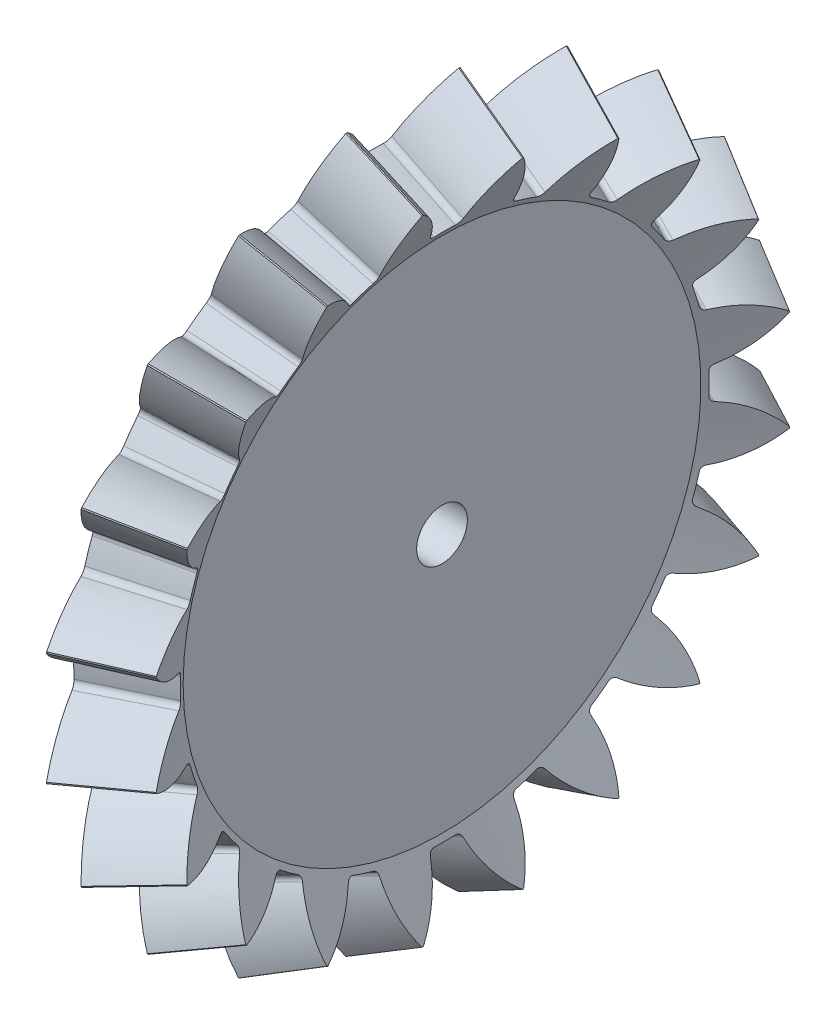
SolidWorks part; units mm, degrees
revolve "Base-Revolve" add sketch "BasProSke" angle 360 about L0 other way angle 9
sketch "BasProSke" plane through (0, 0, 0) normal (0, 1, 0) x (1, 0, 0)
  line L0 (-10, 0) -> (60, 0) construction
  line L1 (0, 0) -> (0, 45.9553)
  line L2 (0, 0) -> (11.6301, 0)
  line L3 (11.6301, 0) -> (11.6301, 40.8173)
  line L4 (104.0224, 0) -> (-25.9395, 64.9809) construction
  line L5 (0, 45.9553) -> (5.478, 56.9113)
  line L6 (104.0224, 0) -> (-24.5296, 74.2412) construction
  line L7 (104.0224, 0) -> (0, 45.9553) construction
  line L8 (5.478, 56.9113) -> (16.4956, 50.5484)
  line L9 (16.4956, 50.5484) -> (11.6301, 40.8173)
  line L10 (2.4224, 50.8) -> (-9.562, 50.8) construction
  dimension "D1" = 91.9106
  dimension "D2" = 104.0224
  dimension "D3" = 113.5923
  dimension "D4" = 3.442
ref_plane "Plane1" through (0, 0, 0) normal (0, 0, 1) x (1, 0, 0)
ref_plane "Plane2" through (0, 0, 0) normal (0, 1, 0) x (1, 0, 0)
ref_plane "Plane3" through (0, 0, 0) normal (1, 0, 0) x (0, 0, -1)
sketch "HoldingSke" plane through (0, 0, 0) normal (0, 1, 0) x (1, 0, 0)
  line L0 (0, 0) -> (119.341, -43.4366)
  line L1 (-15, 0) -> (100, 0) construction
  line L2 (0, 0) -> (-3.4367, 41.6724)
  line L3 (0, 0) -> (-11.863, 4.5341)
  line L4 (0, 0) -> (8.1152, 2.9537)
  line L5 (0, 0) -> (-66.6361, -24.8533)
  line L6 (0, 0) -> (-10.5278, -7.1032)
  line L7 (-3.4367, 41.6724) -> (46.0871, 133.1495)
  line L8 (-76.2, 54.61) -> (-54.9402, 54.61)
  line L9 (-71.009, 38.7566) -> (-53.1078, 45.2721)
  line L10 (-76.2, 71.12) -> (104.1128, 71.12)
  line L11 (0, 0) -> (-12.7, 0)
  line L12 (-76.2, 101.6) -> (-76.0095, 101.6)
  line L13 (24.9733, 27.94) -> (52.9484, 28.5968)
  line L14 (24.9733, 27.94) -> (25.0241, 27.9398)
  line L15 (24.9733, 27.94) -> (100.4104, 29.05)
  line L16 (-3.4367, 41.6724) -> (95.4653, -41.3162)
  circle A0 centre (0, 0) radius 9.525
  circle A1 centre (0, 0) radius 15.24
  circle A2 centre (0, 0) radius 15.24
  circle A3 centre (0, 0) radius 9.525
  dimension "Num_teeth" = 20
  dimension "Pitch_radius" = 180.3128
  dimension "Width" = 12.7
ref_plane "ToothPln" through (2.739, 51.4333, 0) normal (-0.8944, 0.4472, 0) x (0, 0, -1)
ref_plane "ToothPln2" through (83.2179, -41.6089, 0) normal (-0.8944, 0.4472, 0) x (0, 0, 1)
sketch "TooCutSke" plane through (2.739, 51.4333, 0) normal (-0.8944, 0.4472, 0) x (0, 0, -1)
  line L2 (0, 51.508) -> (270.6104, -1657.059) construction
  line L3 (0, 51.508) -> (146.0561, -1760.7306) construction
  line L4 (0, -15.621) -> (0, 105.791) construction
  line L6 (-24.765, -6.1246) -> (21.082, -6.1246) construction
  line L7 (7.9469, 1.3335) -> (4.069, 1.0209) construction
  arc A0 (-9.8853, -6.4401) -> (9.8853, -6.4401) centre (0, 51.508) ccw
  arc A1 (-1.8822, 5.0794) -> (1.8822, 5.0794) centre (0, 51.508) ccw
  circle A2 centre (0, 51.508) radius 50.8 construction
  circle A3 centre (0, 51.508) radius 47.7364 construction
  arc A4 (2.8964, 4.3275) -> (1.8822, 5.0794) centre (1.9229, 4.0744) ccw
  arc A5 (2.8964, 4.3275) -> (9.8853, -6.4401) centre (22.5626, 9.4403) ccw
  arc A6 (-9.8853, -6.4401) -> (-2.8964, 4.3275) centre (-22.5626, 9.4403) ccw
  arc A7 (-1.8822, 5.0794) -> (-2.8964, 4.3275) centre (-1.9229, 4.0744) ccw
  ellipse E0 centre (0, 44.7784) end of major axis (56.9113, 44.7784) minor radius 50.903 construction
sketch "TooCutSke2" plane through (83.2179, -41.6089, 0) normal (-0.8944, 0.4472, 0) x (0, 0, 1)
  line L0 (0, 0) -> (0, 68.072) construction
  line L2 (21.082, 41.1037) -> (-20.32, 41.1037) construction
  circle A0 centre (0, 46.5202) radius 0.0127
  ellipse E1 centre (0, 0) end of major axis (-45.9553, 0) minor radius 41.1037 construction
loft "ToothCut" cut profiles "TooCutSke2", "TooCutSke"
pattern_circular "TeethCuts" count 20 every 18 about axis through (-10, 0, 0) along (1, 0, 0) of "ToothCut"
sketch "HubSke" plane through (0, 0, 0) normal (-1, 0, 0) x (0, 0, 1)
  circle A0 centre (0, 0) radius 15.24
  dimension "Diameter" = 30.48
extrude "Hub" add sketch "HubSke" along normal blind 0.0001
sketch "BorSke" plane through (0, 0, 0) normal (1, 0, 0) x (0, 0, -1)
  circle A0 centre (0, 0) radius 4
  dimension "Diameter" = 8
extrude "Bore" cut sketch "BorSke" along normal mid plane 208.0448
sketch "KeySke" plane through (0, 0, 0) normal (1, 0, 0) x (0, 0, -1)
  line L0 (-2.3813, 0) -> (-2.3813, 11.7348)
  line L1 (-2.3813, 11.7348) -> (2.3813, 11.7348)
  line L2 (2.3813, 11.7348) -> (2.3813, 0)
  line L3 (0, 0) -> (0, 34) construction
  line L4 (-2.3813, 0) -> (2.3813, 0)
  dimension "Offset" = 11.7348
extrude "Keyway" [suppressed] cut sketch "KeySke" along normal mid plane 208.0448
pattern_circular "Keyway2" [suppressed] count 2 every 90 about axis through (-10, 0, 0) along (1, 0, 0)
equation "' \"Pitch@HoldingSke\" = 4"
equation "' \"Num_teeth@HoldingSke\" = 12"
equation "' \"Mating_teeth@HoldingSke\" = 20"
equation "' \"Ap@HoldingSke\" =  20"
equation "' \"Ap@HoldingSke\" = 20"
equation "' \"Width@HoldingSke\" = 0.5"
equation "' \"Hub_dia@HoldingSke\"= 2"
equation "' \"Hub_dia@HoldingSke\" = 2"
equation "' \"Mounting_dist@HoldingSke\" = 3"
equation "' \"Bore@HoldingSke\" = 0.75"
equation "' \"T_dim@HoldingSke\" = 0.85"
equation "' \"Width@KeySke\" = 0.25"
equation "' \"Show_teeth@HoldingSke\" = 100"
equation "' \"Backlash@HoldingSke\" = 0.009"
equation "' \"Addendum_fac@HoldingSke\" = 1.0"
equation "' \"Dedendum_fac@HoldingSke\" = 1.188"
equation "' \"Dedendum_add@HoldingSke\" = 0.002"
equation "' \"Clearance_fac@HoldingSke\" = 0.188"
equation "' \"Addendum_fac@HoldingSke\" = 0.54 + 0.46 / (\"Num_teeth@HoldingSke\" /  \"Mating_teeth@HoldingSke\" ) ^ 2"
equation " \"Addendum_fac@HoldingSke\" = 2 - (0.54 + 0.46 / (\"Mating_teeth@HoldingSke\" /  \"Num_teeth@HoldingSke\" ) ^ 2)"
equation "\"Dedendum_fac@HoldingSke\" = 2.188 - \"Addendum_fac@HoldingSke\""
equation "\"Pitch_rad@BasProSke\" = \"Num_teeth@HoldingSke\" / \"Pitch@HoldingSke\" / 2"
equation "\"Pitch_ang@BasProSke\" = atn(\"Num_teeth@HoldingSke\" / \"Mating_teeth@HoldingSke\") * (180 / 3.14159265)"
equation "\"Addendum@BasProSke\" = \"Addendum_fac@HoldingSke\" / \"Pitch@HoldingSke\""
equation "\"Dedendum_plus@BasProSke\" = (\"Dedendum_fac@HoldingSke\" / \"Pitch@HoldingSke\" + \"Dedendum_add@HoldingSke\") * 1.25"
equation "\"Face_wid@BasProSke\" = \"Width@HoldingSke\""
equation "\"Radius@TooCutSke\" = ((\"Num_teeth@HoldingSke\" + 2 * \"Addendum_fac@HoldingSke\") / \"Pitch@HoldingSke\" ) / 2"
equation "\"Overcut_dia@TooCutSke\" =  1.02 * (\"Num_teeth@HoldingSke\" + 2 * \"Addendum_fac@HoldingSke\") / \"Pitch@HoldingSke\""
equation "\"Pitch_dia@TooCutSke\" = \"Num_teeth@HoldingSke\" / \"Pitch@HoldingSke\""
equation "\"Base_dia@TooCutSke\" = \"Num_teeth@HoldingSke\" / \"Pitch@HoldingSke\" * cos((\"Ap@HoldingSke\"  * 3.14159265 / 180))"
equation "'  \"Root_dia@TooCutSke\" =  (\"Num_teeth@HoldingSke\" + 2) / \"Pitch@HoldingSke\" - 2 * (\"Addendum_fac@HoldingSke\" + \"Dedendum_fac@HoldingSke\") / \"Pitch@HoldingSke\" - \"Dedendum_add@HoldingSke\" * 2"
equation "'  \"Root_dia@TooCutSke\" = (\"Num_teeth@HoldingSke\" + 2) / \"Pitch@HoldingSke\" - 2 * (\"Addendum_fac@HoldingSke\" + \"Dedendum_fac@HoldingSke\") / \"Pitch@HoldingSke\" - \"Dedendum_add@HoldingSke\" * 2"
equation "\"Root_dia@TooCutSke\" =  \"Num_teeth@HoldingSke\" / \"Pitch@HoldingSke\" -  2 * \"Dedendum_fac@HoldingSke\" / \"Pitch@HoldingSke\" - \"Dedendum_add@HoldingSke\" * 2"
equation "\"Half_ang@TooCutSke\" = 180 / \"Num_teeth@HoldingSke\""
equation "\"Half_CT@TooCutSke\" = \"Num_teeth@HoldingSke\" / \"Pitch@HoldingSke\" * sin((3.14159265 / 2 / \"Num_teeth@HoldingSke\")) / 2 - 2 * \"Backlash@HoldingSke\" / 4"
equation "\"Flank_rad@TooCutSke\" = \"Num_teeth@HoldingSke\" / \"Pitch@HoldingSke\" / 5"
equation "\"Root_fillet@TooCutSke\" = \"Clearance_fac@HoldingSke\" / \"Pitch@HoldingSke\" + \"Dedendum_add@HoldingSke\""
equation "\"Offset@ToothPln2\"  = \"Num_teeth@HoldingSke\" / \"Pitch@HoldingSke\" / 2 / sin(atn(\"Num_teeth@HoldingSke\" / \"Mating_teeth@HoldingSke\"))"
equation "\"Dedendum_plus@TooCutSke2\" = \"Dedendum_plus@BasProSke\""
equation "\"MHD@HoldingSke\" = \"Num_teeth@HoldingSke\" / \"Pitch@HoldingSke\" - 2 * \"Dedendum_plus@BasProSke\" * cos(atn(\"Num_teeth@HoldingSke\" / \"Mating_teeth@HoldingSke\"))"
equation "\"MBD@HoldingSke\" = \"Num_teeth@HoldingSke\" / \"Pitch@HoldingSke\" - 2 * \"Dedendum_plus@BasProSke\" * cos(atn(\"Num_teeth@HoldingSke\" / \"Mating_teeth@HoldingSke\")) - 0.002"
equation "\"MnMD@HoldingSke\" =  \"Num_teeth@HoldingSke\" / \"Pitch@HoldingSke\" / 2 / (\"Num_teeth@HoldingSke\" / \"Mating_teeth@HoldingSke\") + \"Dedendum_plus@BasProSke\" * sin(atn(\"Num_teeth@HoldingSke\" / \"Mating_teeth@HoldingSke\"))"
equation "\"OAL@HoldingSke\" = \"MnMD@HoldingSke\""
equation "\"MHD@HoldingSke\" = ((sgn( \"MHD@HoldingSke\" - \"Hub_dia@HoldingSke\" )-1)*( \"MHD@HoldingSke\" - \"Hub_dia@HoldingSke\" ))/-2+ \"Hub_dia@HoldingSke\""
equation "\"MBD@HoldingSke\" = ((sgn( \"MBD@HoldingSke\" - \"Bore@HoldingSke\" )-1)*( \"MBD@HoldingSke\" - \"Bore@HoldingSke\" ))/-2+ \"Bore@HoldingSke\""
equation "\"Face_wid@BasProSke\" = ((sgn( \"Face_wid@BasProSke\" - \"Offset@ToothPln2\" * 0.9)-1)*( \"Face_wid@BasProSke\" - \"Offset@ToothPln2\" * 0.9))/-2+ \"Offset@ToothPln2\" * 0.9"
equation "\"OAL@HoldingSke\" = ((sgn( \"OAL@HoldingSke\" - \"Mounting_dist@HoldingSke\" )+1)*( \"OAL@HoldingSke\" - \"Mounting_dist@HoldingSke\" ))/2 + \"Mounting_dist@HoldingSke\" + 0.000002"
equation "\"Num_teeth@TeethCuts\" = int( \"Show_teeth@HoldingSke\" ) + 1"
equation "\"Num_teeth@TeethCuts\" = ((sgn( \"Num_teeth@TeethCuts\" - \"Num_teeth@HoldingSke\" )-1)*( \"Num_teeth@TeethCuts\" - \"Num_teeth@HoldingSke\" ))/-2+ \"Num_teeth@HoldingSke\""
equation "\"Num_teeth@TeethCuts\" = ((sgn( \"Num_teeth@TeethCuts\" - 2.0)+1)*( \"Num_teeth@TeethCuts\" - 2.0))/2 +2.0"
equation "\"Angle@TeethCuts\" = 360.0 / \"Num_teeth@HoldingSke\""
equation "\"Diameter@HubSke\" = \"MHD@HoldingSke\""
equation "\"Length@Hub\" = \"OAL@HoldingSke\" - \"MnMD@HoldingSke\" + 0.000002"
equation "\"D1@Bore\" = \"OAL@HoldingSke\" * 2.0"
equation "\"D1@Keyway\" = \"OAL@HoldingSke\" * 2.0"
equation "\"Offset@KeySke\" = \"T_dim@HoldingSke\" - \"MBD@HoldingSke\" / 2.0"
